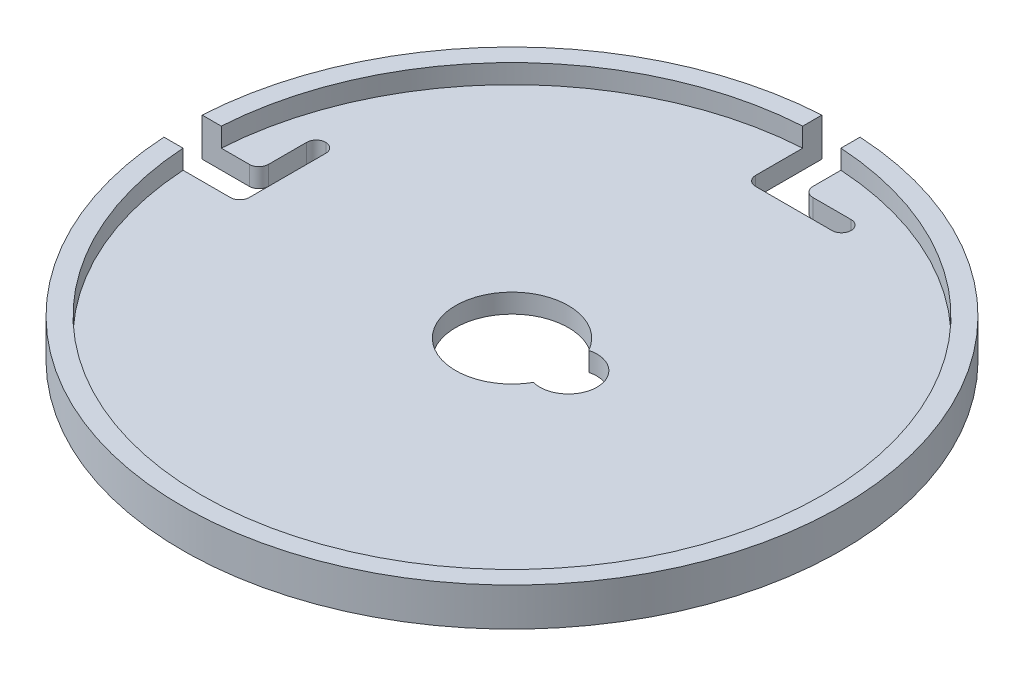
SolidWorks part; units mm, degrees
ref_plane "Front Plane" through (0, 0, 0) normal (0, 0, 1) x (1, 0, 0)
ref_plane "Top Plane" through (0, 0, 0) normal (0, 1, 0) x (1, 0, 0)
ref_plane "Right Plane" through (0, 0, 0) normal (1, 0, 0) x (0, 0, -1)
sketch "Sketch1" plane through (0, 0, 0) normal (0, 1, 0) x (1, 0, 0)
  circle A0 centre (0, 0) radius 32.5
  dimension "D1" = 65
extrude "Outer DIsk" add sketch "Sketch1" along normal blind 2
shell "Enclosement" thickness 2 removed face at (0, 2, 32.5) outward yes
sketch "Sketch2" plane through (0, 0, 0) normal (0, 1, 0) x (1, 0, 0)
  line L0 (-2, 34.5) -> (-2, 26.5)
  line L9 (-2, 34.5) -> (2, 34.5)
  line L10 (2, 34.5) -> (2, 28.5)
  line L11 (-2, 26.5) -> (8, 26.5)
  line L12 (2, 28.5) -> (8, 28.5)
  line L13 (8, 26.5) -> (8, 28.5)
  line L14 (2, 28.5) -> (2, 26.5)
  circle A1 centre (0, 0) radius 34.5 construction
  circle A3 centre (0, 0) radius 26.5 construction
  point P2 (0, 34.5)
  dimension "D1" = 4
  dimension "D2" = 8
  dimension "D3" = 2
  dimension "D4" = 10
extrude "Hook Release" cut sketch "Sketch2" against normal through all both and the other way through all contours L10 L9 L0 L11 L13 L12
sketch "Sketch3" plane through (0, 0, 0) normal (0, 1, 0) x (1, 0, 0)
  circle A0 centre (0, 0) radius 28.75 construction
  circle A1 centre (0, 0) radius 5.9
  circle A2 centre (5.9, 0) radius 3
  dimension "D1" = 11.8
  dimension "D3" = 6
  dimension "D2" = 5.9
pattern_circular "CirPattern1" count 2 over 90 about axis through (0, 2, 0) along (0, 1, 0) of "Hook Release"
extrude "Servo Motor Cutout" cut sketch "Sketch3" against normal through all both and the other way through all contours A2 A1 | A1 A2 | A1 A2 region at (4.4996, 0, 0) region at (7.026, 0, 0) region at (-0.586, 0, 0)
fillet "Fillet1" radius 1 8 edges at (-26.5, -1, 2) (-26.5, -1, -8) (-28.5, -1, -8) (-28.5, -1, -2) (8, -1, -26.5) (-2, -1, -26.5) (8, -1, -28.5) (2, -1, -28.5)
